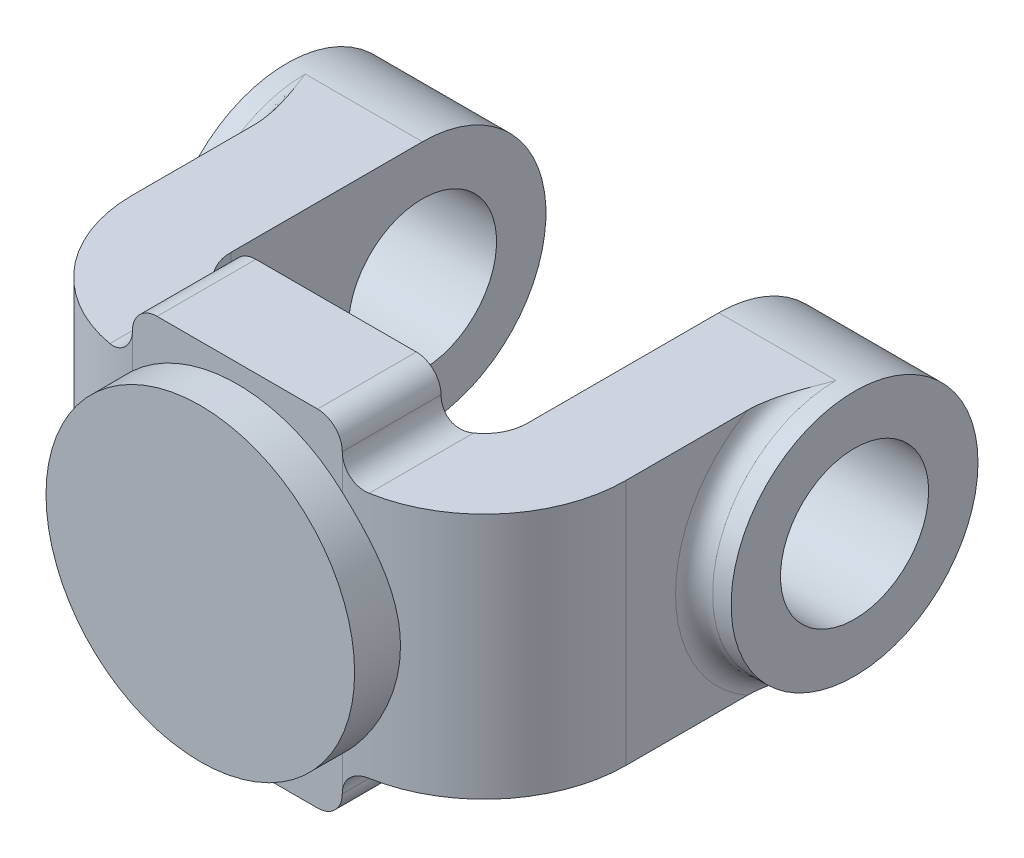
SolidWorks part; units mm, degrees
ref_plane "Спереди" through (0, 0, 0) normal (0, 0, 1) x (1, 0, 0)
ref_plane "Сверху" through (0, 0, 0) normal (0, 1, 0) x (1, 0, 0)
ref_plane "Справа" through (0, 0, 0) normal (1, 0, 0) x (0, 0, -1)
sketch "Эскиз1" plane through (0, 0, 0) normal (0, 0, 1) x (1, 0, 0)
  line L1 (-17, -28) -> (17, -28)
  line L2 (-17, -28) -> (-17, 28)
  line L3 (-17, 28) -> (17, 28)
  line L4 (17, -28) -> (17, 28)
  line L5 (-17, -28) -> (17, 28) construction
  line L6 (-17, 28) -> (17, -28) construction
  point P0 (0, 0)
  dimension "D1" = 34
  dimension "D2" = 56
extrude "Бобышка-Вытянуть1" add sketch "Эскиз1" along normal blind 16
sketch "Эскиз2" plane through (0, 0, 16) normal (0, 0, 1) x (1, 0, 0)
  line L1 (-40, -20) -> (40, -20)
  line L2 (-40, -20) -> (-40, 20)
  line L3 (-40, 20) -> (40, 20)
  line L4 (40, -20) -> (40, 20)
  line L5 (-40, -20) -> (40, 20) construction
  line L6 (-40, 20) -> (40, -20) construction
  point P0 (0, 0)
  dimension "D1" = 40
  dimension "D2" = 80
extrude "Бобышка-Вытянуть3" add sketch "Эскиз2" against normal blind 16
sketch "Эскиз3" plane through (40, 0, 0) normal (1, 0, 0) x (0, 0, -1)
  line L0 (-16, 20) -> (0, 20) construction
  line L1 (-16, -20) -> (38, -20)
  line L2 (-16, -20) -> (-16, 20)
  line L3 (-16, 20) -> (38, 20)
  arc A0 (38, -20) -> (38, 20) centre (38, 0) ccw
  dimension "D1" = 54
extrude "Бобышка-Вытянуть4" add sketch "Эскиз3" against normal blind 16
sketch "Эскиз4" plane through (40, 0, 0) normal (1, 0, 0) x (0, 0, -1)
  circle A0 centre (38, 0) radius 20
  arc A1 (38, -20) -> (38, 20) centre (38, 0) ccw construction
extrude "Бобышка-Вытянуть5" add sketch "Эскиз4" along normal blind 6
sketch "Эскиз5" plane through (46, 0, 0) normal (1, 0, 0) x (0, 0, -1)
  circle A0 centre (38, 0) radius 12
  dimension "D1" = 24
extrude "Вырез-Вытянуть1" cut sketch "Эскиз5" against normal through all
mirror "Зеркальное отражение1" about plane through (0, 0, 0) normal (1, 0, 0) of "Бобышка-Вытянуть5", "Бобышка-Вытянуть4", "Вырез-Вытянуть1"
fillet "Скругление1" radius 7 2 edges at (-24, 0, 0) (24, 0, 0)
fillet "Скругление2" radius 23 2 edges at (40, 0, 16) (-40, 0, 16)
fillet "Скругление3" radius 3 2 edges at (40, 0, -18) (-40, 0, -18)
fillet "Скругление4" radius 4 8 edges at (17, 28, 8) (17, 20, 8) (-17, 28, 8) (-17, 20, 8) (17, -20, 8) (17, -28, 8) (-17, -28, 8) (-17, -20, 8)
ref_plane "Плоскость4" through (0, 0, 22) normal (0, 0, 1) x (1, 0, 0)
sketch "Эскиз6" plane through (0, 0, 22) normal (0, 0, 1) x (1, 0, 0)
  circle A0 centre (0, 0) radius 25
  dimension "D1" = 50
extrude "Бобышка-Вытянуть6" add sketch "Эскиз6" against normal up to body separate body
